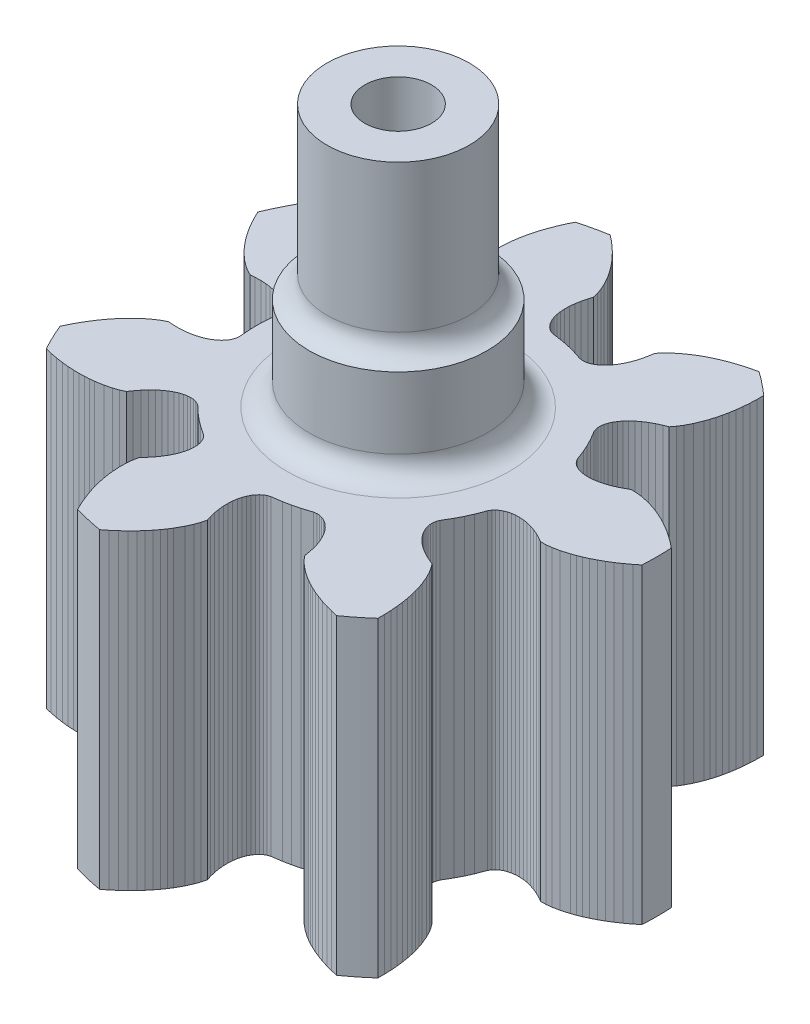
SolidWorks part; units mm, degrees
ref_plane "Front Plane" through (0, 0, 0) normal (0, 0, 1) x (1, 0, 0)
ref_plane "Top Plane" through (0, 0, 0) normal (0, 1, 0) x (1, 0, 0)
ref_plane "Right Plane" through (0, 0, 0) normal (1, 0, 0) x (0, 0, -1)
sketch "Sketch1" plane through (0, 0, 0) normal (0, 1, 0) x (1, 0, 0)
  circle A0 centre (0, 0) radius 2
  dimension "D1" = 4
extrude "Boss-Extrude1" add sketch "Sketch1" along normal blind 2.1
sketch "Sketch2" plane through (0, 2.1, 0) normal (0, 1, 0) x (1, 0, 0)
  circle A0 centre (0, 0) radius 1.6
  dimension "D1" = 3.2
extrude "Boss-Extrude3" add sketch "Sketch2" along normal blind 3.8
sketch "Sketch4" plane through (0, 0, 0) normal (0, -1, 0) x (1, 0, 0)
  line L420 (-1.6777, -5.4575) -> (-1.7402, -5.3144)
  line L421 (-1.7402, -5.3144) -> (-1.7939, -5.1757)
  line L422 (-1.7939, -5.1757) -> (-1.8392, -5.0423)
  line L423 (-1.8392, -5.0423) -> (-1.8764, -4.916)
  line L424 (-1.8764, -4.916) -> (-1.9071, -4.7932)
  line L425 (-1.9071, -4.7932) -> (-1.9311, -4.676)
  line L426 (-1.9311, -4.676) -> (-1.9488, -4.5668)
  line L427 (-1.9488, -4.5668) -> (-1.961, -4.464)
  line L428 (-1.961, -4.464) -> (-1.9715, -4.2798)
  line L429 (-1.9715, -4.2798) -> (-1.9674, -4.1246)
  line L430 (-1.9674, -4.1246) -> (-1.9537, -4.0009)
  line L431 (-1.9537, -4.0009) -> (-1.9303, -3.8867)
  line L432 (-1.9303, -3.8867) -> (-1.8594, -3.8097)
  line L433 (-1.8594, -3.8097) -> (-1.7784, -3.7125)
  line L434 (-1.7784, -3.7125) -> (-1.7087, -3.6155)
  line L435 (-1.7087, -3.6155) -> (-1.6501, -3.5195)
  line L436 (-1.6501, -3.5195) -> (-1.6023, -3.4251)
  line L437 (-1.6023, -3.4251) -> (-1.5652, -3.3333)
  line L438 (-1.5652, -3.3333) -> (-1.5384, -3.2446)
  line L439 (-1.5384, -3.2446) -> (-1.5215, -3.1597)
  line L440 (-1.5215, -3.1597) -> (-1.5143, -3.0795)
  line L441 (-1.5143, -3.0795) -> (-1.5162, -3.0043)
  line L442 (-1.5162, -3.0043) -> (-1.5269, -2.935)
  line L443 (-1.5269, -2.935) -> (-1.5457, -2.8721)
  line L444 (-1.5457, -2.8721) -> (-1.5723, -2.8162)
  line L445 (-1.5723, -2.8162) -> (-1.606, -2.7677)
  line L446 (-1.606, -2.7677) -> (-1.6572, -2.7183)
  line L447 (-1.6572, -2.7183) -> (-1.8447, -2.5928)
  line L448 (-1.8447, -2.5928) -> (-1.984, -2.4878)
  line L449 (-1.984, -2.4878) -> (-2.1173, -2.3754)
  line L450 (-2.1173, -2.3754) -> (-2.2814, -2.2205)
  line L451 (-2.2814, -2.2205) -> (-2.341, -2.1815)
  line L452 (-2.341, -2.1815) -> (-2.3957, -2.1595)
  line L453 (-2.3957, -2.1595) -> (-2.4562, -2.146)
  line L454 (-2.4562, -2.146) -> (-2.5217, -2.1417)
  line L455 (-2.5217, -2.1417) -> (-2.5917, -2.1467)
  line L456 (-2.5917, -2.1467) -> (-2.6653, -2.1615)
  line L457 (-2.6653, -2.1615) -> (-2.742, -2.1865)
  line L458 (-2.742, -2.1865) -> (-2.8209, -2.2218)
  line L459 (-2.8209, -2.2218) -> (-2.9014, -2.2676)
  line L460 (-2.9014, -2.2676) -> (-2.9827, -2.3243)
  line L461 (-2.9827, -2.3243) -> (-3.0641, -2.3918)
  line L462 (-3.0641, -2.3918) -> (-3.1447, -2.4703)
  line L463 (-3.1447, -2.4703) -> (-3.2237, -2.5599)
  line L464 (-3.2237, -2.5599) -> (-3.3005, -2.6605)
  line L465 (-3.3005, -2.6605) -> (-3.3598, -2.7467)
  line L466 (-3.3598, -2.7467) -> (-3.4659, -2.795)
  line L467 (-3.4659, -2.795) -> (-3.5835, -2.8358)
  line L468 (-3.5835, -2.8358) -> (-3.7338, -2.8744)
  line L469 (-3.7338, -2.8744) -> (-3.9158, -2.9052)
  line L470 (-3.9158, -2.9052) -> (-4.0187, -2.9161)
  line L471 (-4.0187, -2.9161) -> (-4.1291, -2.9232)
  line L472 (-4.1291, -2.9232) -> (-4.2487, -2.9258)
  line L473 (-4.2487, -2.9258) -> (-4.3752, -2.9233)
  line L474 (-4.3752, -2.9233) -> (-4.5067, -2.9151)
  line L475 (-4.5067, -2.9151) -> (-4.6468, -2.9006)
  line L476 (-4.6468, -2.9006) -> (-4.794, -2.8791)
  line L477 (-4.794, -2.8791) -> (-4.9474, -2.85)
  line L478 (-4.9474, -2.85) -> (-5.0902, -2.8167)
  line L479 (-5.3759, -2.2235) -> (-5.3129, -2.0911)
  line L480 (-5.3129, -2.0911) -> (-5.2399, -1.953)
  line L481 (-5.2399, -1.953) -> (-5.165, -1.8245)
  line L482 (-5.165, -1.8245) -> (-5.089, -1.7059)
  line L483 (-5.089, -1.7059) -> (-5.0134, -1.5981)
  line L484 (-5.0134, -1.5981) -> (-4.9365, -1.4976)
  line L485 (-4.9365, -1.4976) -> (-4.8599, -1.4057)
  line L486 (-4.8599, -1.4057) -> (-4.7855, -1.3238)
  line L487 (-4.7855, -1.3238) -> (-4.7128, -1.2502)
  line L488 (-4.7128, -1.2502) -> (-4.5753, -1.1271)
  line L489 (-4.5753, -1.1271) -> (-4.4514, -1.0336)
  line L490 (-4.4514, -1.0336) -> (-4.3462, -0.9671)
  line L491 (-4.3462, -0.9671) -> (-4.2422, -0.9142)
  line L492 (-4.2422, -0.9142) -> (-4.1379, -0.9217)
  line L493 (-4.1379, -0.9217) -> (-4.0114, -0.9244)
  line L494 (-4.0114, -0.9244) -> (-3.8921, -0.9184)
  line L495 (-3.8921, -0.9184) -> (-3.7804, -0.9043)
  line L496 (-3.7804, -0.9043) -> (-3.6769, -0.8828)
  line L497 (-3.6769, -0.8828) -> (-3.5819, -0.8546)
  line L498 (-3.5819, -0.8546) -> (-3.4959, -0.8203)
  line L499 (-3.4959, -0.8203) -> (-3.4191, -0.7805)
  line L500 (-3.4191, -0.7805) -> (-3.3518, -0.7361)
  line L501 (-3.3518, -0.7361) -> (-3.2942, -0.6878)
  line L502 (-3.2942, -0.6878) -> (-3.2467, -0.6363)
  line L503 (-3.2467, -0.6363) -> (-3.2093, -0.5823)
  line L504 (-3.2093, -0.5823) -> (-3.1821, -0.5267)
  line L505 (-3.1821, -0.5267) -> (-3.1652, -0.4701)
  line L506 (-3.1652, -0.4701) -> (-3.1585, -0.3992)
  line L507 (-3.1585, -0.3992) -> (-3.1773, -0.1744)
  line L508 (-3.1773, -0.1744) -> (-3.1821, 0)
  line L509 (-3.1821, 0) -> (-3.1773, 0.1743)
  line L510 (-3.1773, 0.1743) -> (-3.1585, 0.3991)
  line L511 (-3.1585, 0.3991) -> (-3.1652, 0.47)
  line L512 (-3.1652, 0.47) -> (-3.1821, 0.5266)
  line L513 (-3.1821, 0.5266) -> (-3.2093, 0.5822)
  line L514 (-3.2093, 0.5822) -> (-3.2467, 0.6362)
  line L515 (-3.2467, 0.6362) -> (-3.2942, 0.6877)
  line L516 (-3.2942, 0.6877) -> (-3.3518, 0.7361)
  line L517 (-3.3518, 0.7361) -> (-3.4191, 0.7805)
  line L518 (-3.4191, 0.7805) -> (-3.4959, 0.8202)
  line L519 (-3.4959, 0.8202) -> (-3.5819, 0.8545)
  line L520 (-3.5819, 0.8545) -> (-3.6769, 0.8828)
  line L521 (-3.6769, 0.8828) -> (-3.7804, 0.9043)
  line L522 (-3.7804, 0.9043) -> (-3.8921, 0.9183)
  line L523 (-3.8921, 0.9183) -> (-4.0114, 0.9243)
  line L524 (-4.0114, 0.9243) -> (-4.1379, 0.9216)
  line L525 (-4.1379, 0.9216) -> (-4.2422, 0.9142)
  line L526 (-4.2422, 0.9142) -> (-4.3462, 0.967)
  line L527 (-4.3462, 0.967) -> (-4.4514, 1.0335)
  line L528 (-4.4514, 1.0335) -> (-4.5753, 1.127)
  line L529 (-4.5753, 1.127) -> (-4.7128, 1.2501)
  line L530 (-4.7128, 1.2501) -> (-4.7855, 1.3238)
  line L531 (-4.7855, 1.3238) -> (-4.8599, 1.4056)
  line L532 (-4.8599, 1.4056) -> (-4.9365, 1.4975)
  line L533 (-4.9365, 1.4975) -> (-5.0134, 1.598)
  line L534 (-5.0134, 1.598) -> (-5.089, 1.7059)
  line L535 (-5.089, 1.7059) -> (-5.165, 1.8244)
  line L536 (-5.165, 1.8244) -> (-5.2399, 1.9529)
  line L537 (-5.2399, 1.9529) -> (-5.3129, 2.0911)
  line L538 (-5.3129, 2.0911) -> (-5.3759, 2.2234)
  line L539 (-5.0902, 2.8167) -> (-4.9474, 2.8499)
  line L540 (-4.9474, 2.8499) -> (-4.794, 2.879)
  line L541 (-4.794, 2.879) -> (-4.6468, 2.9005)
  line L542 (-4.6468, 2.9005) -> (-4.5067, 2.9151)
  line L543 (-4.5067, 2.9151) -> (-4.3752, 2.9232)
  line L544 (-4.3752, 2.9232) -> (-4.2487, 2.9257)
  line L545 (-4.2487, 2.9257) -> (-4.1291, 2.9231)
  line L546 (-4.1291, 2.9231) -> (-4.0187, 2.916)
  line L547 (-4.0187, 2.916) -> (-3.9158, 2.9051)
  line L548 (-3.9158, 2.9051) -> (-3.7338, 2.8743)
  line L549 (-3.7338, 2.8743) -> (-3.5835, 2.8358)
  line L550 (-3.5835, 2.8358) -> (-3.4659, 2.7949)
  line L551 (-3.4659, 2.7949) -> (-3.3598, 2.7466)
  line L552 (-3.3598, 2.7466) -> (-3.3005, 2.6604)
  line L553 (-3.3005, 2.6604) -> (-3.2237, 2.5598)
  line L554 (-3.2237, 2.5598) -> (-3.1447, 2.4703)
  line L555 (-3.1447, 2.4703) -> (-3.0641, 2.3918)
  line L556 (-3.0641, 2.3918) -> (-2.9827, 2.3242)
  line L557 (-2.9827, 2.3242) -> (-2.9014, 2.2676)
  line L558 (-2.9014, 2.2676) -> (-2.8209, 2.2217)
  line L559 (-2.8209, 2.2217) -> (-2.742, 2.1864)
  line L560 (-2.742, 2.1864) -> (-2.6653, 2.1615)
  line L561 (-2.6653, 2.1615) -> (-2.5917, 2.1466)
  line L562 (-2.5917, 2.1466) -> (-2.5217, 2.1416)
  line L563 (-2.5217, 2.1416) -> (-2.4562, 2.146)
  line L564 (-2.4562, 2.146) -> (-2.3957, 2.1594)
  line L565 (-2.3957, 2.1594) -> (-2.341, 2.1815)
  line L566 (-2.341, 2.1815) -> (-2.2814, 2.2205)
  line L567 (-2.2814, 2.2205) -> (-2.1173, 2.3753)
  line L568 (-2.1173, 2.3753) -> (-1.984, 2.4878)
  line L569 (-1.984, 2.4878) -> (-1.8447, 2.5927)
  line L570 (-1.8447, 2.5927) -> (-1.6572, 2.7182)
  line L571 (-1.6572, 2.7182) -> (-1.606, 2.7676)
  line L572 (-1.606, 2.7676) -> (-1.5723, 2.8161)
  line L573 (-1.5723, 2.8161) -> (-1.5457, 2.8721)
  line L574 (-1.5457, 2.8721) -> (-1.5269, 2.935)
  line L575 (-1.5269, 2.935) -> (-1.5162, 3.0043)
  line L576 (-1.5162, 3.0043) -> (-1.5143, 3.0794)
  line L577 (-1.5143, 3.0794) -> (-1.5215, 3.1597)
  line L578 (-1.5215, 3.1597) -> (-1.5384, 3.2445)
  line L579 (-1.5384, 3.2445) -> (-1.5652, 3.3332)
  line L580 (-1.5652, 3.3332) -> (-1.6023, 3.4251)
  line L581 (-1.6023, 3.4251) -> (-1.6501, 3.5194)
  line L582 (-1.6501, 3.5194) -> (-1.7087, 3.6154)
  line L583 (-1.7087, 3.6154) -> (-1.7784, 3.7125)
  line L584 (-1.7784, 3.7125) -> (-1.8594, 3.8097)
  line L585 (-1.8594, 3.8097) -> (-1.9303, 3.8866)
  line L586 (-1.9303, 3.8866) -> (-1.9537, 4.0009)
  line L587 (-1.9537, 4.0009) -> (-1.9674, 4.1246)
  line L588 (-1.9674, 4.1246) -> (-1.9715, 4.2797)
  line L589 (-1.9715, 4.2797) -> (-1.961, 4.464)
  line L590 (-1.961, 4.464) -> (-1.9488, 4.5668)
  line L591 (-1.9488, 4.5668) -> (-1.9311, 4.6759)
  line L592 (-1.9311, 4.6759) -> (-1.9071, 4.7932)
  line L593 (-1.9071, 4.7932) -> (-1.8764, 4.9159)
  line L594 (-1.8764, 4.9159) -> (-1.8392, 5.0423)
  line L595 (-1.8392, 5.0423) -> (-1.7939, 5.1756)
  line L596 (-1.7939, 5.1756) -> (-1.7402, 5.3143)
  line L597 (-1.7402, 5.3143) -> (-1.6777, 5.4575)
  line L598 (-1.6777, 5.4575) -> (-1.6135, 5.5893)
  line L599 (-0.9715, 5.7358) -> (-0.8565, 5.6449)
  line L600 (-0.8565, 5.6449) -> (-0.7381, 5.543)
  line L601 (-0.7381, 5.543) -> (-0.6295, 5.4414)
  line L602 (-0.6295, 5.4414) -> (-0.5308, 5.3409)
  line L603 (-0.5308, 5.3409) -> (-0.4425, 5.2432)
  line L604 (-0.4425, 5.2432) -> (-0.3616, 5.1459)
  line L605 (-0.3616, 5.1459) -> (-0.2891, 5.0507)
  line L606 (-0.2891, 5.0507) -> (-0.2258, 4.96)
  line L607 (-0.2258, 4.96) -> (-0.1702, 4.8727)
  line L608 (-0.1702, 4.8727) -> (-0.0808, 4.7113)
  line L609 (-0.0808, 4.7113) -> (-0.0172, 4.5697)
  line L610 (-0.0172, 4.5697) -> (0.0242, 4.4523)
  line L611 (0.0242, 4.4523) -> (0.0526, 4.3392)
  line L612 (0.0526, 4.3392) -> (0.0222, 4.2391)
  line L613 (0.0222, 4.2391) -> (-0.0086, 4.1164)
  line L614 (-0.0086, 4.1164) -> (-0.0293, 3.9987)
  line L615 (-0.0293, 3.9987) -> (-0.0405, 3.8868)
  line L616 (-0.0405, 3.8868) -> (-0.0426, 3.7811)
  line L617 (-0.0426, 3.7811) -> (-0.0362, 3.6822)
  line L618 (-0.0362, 3.6822) -> (-0.0218, 3.5907)
  line L619 (-0.0218, 3.5907) -> (-0.0002, 3.5069)
  line L620 (-0.0002, 3.5069) -> (0.0281, 3.4314)
  line L621 (0.0281, 3.4314) -> (0.0624, 3.3646)
  line L622 (0.0624, 3.3646) -> (0.1021, 3.3068)
  line L623 (0.1021, 3.3068) -> (0.1464, 3.2583)
  line L624 (0.1464, 3.2583) -> (0.1946, 3.2194)
  line L625 (0.1946, 3.2194) -> (0.246, 3.1903)
  line L626 (0.246, 3.1903) -> (0.3136, 3.1681)
  line L627 (0.3136, 3.1681) -> (0.537, 3.1363)
  line L628 (0.537, 3.1363) -> (0.708, 3.1022)
  line L629 (0.708, 3.1022) -> (0.8769, 3.0588)
  line L630 (0.8769, 3.0588) -> (1.0919, 2.9904)
  line L631 (1.0919, 2.9904) -> (1.1625, 2.9811)
  line L632 (1.1625, 2.9811) -> (1.2214, 2.985)
  line L633 (1.2214, 2.985) -> (1.2817, 2.9991)
  line L634 (1.2817, 2.9991) -> (1.3427, 3.0236)
  line L635 (1.3427, 3.0236) -> (1.4035, 3.0585)
  line L636 (1.4035, 3.0585) -> (1.4634, 3.1038)
  line L637 (1.4634, 3.1038) -> (1.5217, 3.1596)
  line L638 (1.5217, 3.1596) -> (1.5775, 3.2256)
  line L639 (1.5775, 3.2256) -> (1.6301, 3.3019)
  line L640 (1.6301, 3.3019) -> (1.6788, 3.3882)
  line L641 (1.6788, 3.3882) -> (1.7228, 3.4843)
  line L642 (1.7228, 3.4843) -> (1.7613, 3.59)
  line L643 (1.7613, 3.59) -> (1.7937, 3.705)
  line L644 (1.7937, 3.705) -> (1.8192, 3.829)
  line L645 (1.8192, 3.829) -> (1.8352, 3.9324)
  line L646 (1.8352, 3.9324) -> (1.9099, 4.0219)
  line L647 (1.9099, 4.0219) -> (1.9981, 4.1097)
  line L648 (1.9981, 4.1097) -> (2.1168, 4.2097)
  line L649 (2.1168, 4.2097) -> (2.2674, 4.3164)
  line L650 (2.2674, 4.3164) -> (2.3554, 4.3709)
  line L651 (2.3554, 4.3709) -> (2.4518, 4.4251)
  line L652 (2.4518, 4.4251) -> (2.5584, 4.4794)
  line L653 (2.5584, 4.4794) -> (2.6735, 4.532)
  line L654 (2.6735, 4.532) -> (2.7955, 4.5817)
  line L655 (2.7955, 4.5817) -> (2.928, 4.6294)
  line L656 (2.928, 4.6294) -> (3.0699, 4.6739)
  line L657 (3.0699, 4.6739) -> (3.2208, 4.7143)
  line L658 (3.2208, 4.7143) -> (3.3639, 4.7463)
  line L659 (3.8787, 4.3357) -> (3.8793, 4.1891)
  line L660 (3.8793, 4.1891) -> (3.8735, 4.033)
  line L661 (3.8735, 4.033) -> (3.8618, 3.8847)
  line L662 (3.8618, 3.8847) -> (3.8448, 3.7449)
  line L663 (3.8448, 3.7449) -> (3.8234, 3.615)
  line L664 (3.8234, 3.615) -> (3.7978, 3.4911)
  line L665 (3.7978, 3.4911) -> (3.7686, 3.375)
  line L666 (3.7686, 3.375) -> (3.7371, 3.269)
  line L667 (3.7371, 3.269) -> (3.7036, 3.1711)
  line L668 (3.7036, 3.1711) -> (3.6331, 3.0005)
  line L669 (3.6331, 3.0005) -> (3.562, 2.8625)
  line L670 (3.562, 2.8625) -> (3.4961, 2.757)
  line L671 (3.4961, 2.757) -> (3.4253, 2.6643)
  line L672 (3.4253, 2.6643) -> (3.3281, 2.6257)
  line L673 (3.3281, 2.6257) -> (3.213, 2.5732)
  line L674 (3.213, 2.5732) -> (3.1081, 2.516)
  line L675 (3.1081, 2.516) -> (3.0136, 2.4549)
  line L676 (3.0136, 2.4549) -> (2.9296, 2.3907)
  line L677 (2.9296, 2.3907) -> (2.8563, 2.324)
  line L678 (2.8563, 2.324) -> (2.7937, 2.2557)
  line L679 (2.7937, 2.2557) -> (2.7417, 2.1866)
  line L680 (2.7417, 2.1866) -> (2.7003, 2.1174)
  line L681 (2.7003, 2.1174) -> (2.6695, 2.0489)
  line L682 (2.6695, 2.0489) -> (2.649, 1.9819)
  line L683 (2.649, 1.9819) -> (2.6387, 1.917)
  line L684 (2.6387, 1.917) -> (2.6383, 1.8551)
  line L685 (2.6383, 1.8551) -> (2.6476, 1.7967)
  line L686 (2.6476, 1.7967) -> (2.6724, 1.73)
  line L687 (2.6724, 1.73) -> (2.7869, 1.5356)
  line L688 (2.7869, 1.5356) -> (2.8668, 1.3806)
  line L689 (2.8668, 1.3806) -> (2.9382, 1.2215)
  line L690 (2.9382, 1.2215) -> (3.0188, 1.0107)
  line L691 (3.0188, 1.0107) -> (3.0555, 0.9498)
  line L692 (3.0555, 0.9498) -> (3.0953, 0.9061)
  line L693 (3.0953, 0.9061) -> (3.144, 0.8678)
  line L694 (3.144, 0.8678) -> (3.2011, 0.8354)
  line L695 (3.2011, 0.8354) -> (3.2663, 0.8096)
  line L696 (3.2663, 0.8096) -> (3.3391, 0.791)
  line L697 (3.3391, 0.791) -> (3.419, 0.7802)
  line L698 (3.419, 0.7802) -> (3.5054, 0.7777)
  line L699 (3.5054, 0.7777) -> (3.5979, 0.7842)
  line L700 (3.5979, 0.7842) -> (3.6957, 0.7999)
  line L701 (3.6957, 0.7999) -> (3.7983, 0.8255)
  line L702 (3.7983, 0.8255) -> (3.905, 0.8612)
  line L703 (3.905, 0.8612) -> (4.0151, 0.9076)
  line L704 (4.0151, 0.9076) -> (4.1279, 0.9649)
  line L705 (4.1279, 0.9649) -> (4.2187, 1.0169)
  line L706 (4.2187, 1.0169) -> (4.3353, 1.0144)
  line L707 (4.3353, 1.0144) -> (4.4589, 1.0001)
  line L708 (4.4589, 1.0001) -> (4.6111, 0.9696)
  line L709 (4.6111, 0.9696) -> (4.7884, 0.9184)
  line L710 (4.7884, 0.9184) -> (4.8859, 0.8836)
  line L711 (4.8859, 0.8836) -> (4.9884, 0.8421)
  line L712 (4.9884, 0.8421) -> (5.0973, 0.7926)
  line L713 (5.0973, 0.7926) -> (5.2102, 0.7354)
  line L714 (5.2102, 0.7354) -> (5.3251, 0.671)
  line L715 (5.3251, 0.671) -> (5.445, 0.5972)
  line L716 (5.445, 0.5972) -> (5.5683, 0.5139)
  line L717 (5.5683, 0.5139) -> (5.6939, 0.4211)
  line L718 (5.6939, 0.4211) -> (5.8081, 0.3292)
  line L719 (5.8081, -0.3293) -> (5.6939, -0.4212)
  line L720 (5.6939, -0.4212) -> (5.5683, -0.514)
  line L721 (5.5683, -0.514) -> (5.445, -0.5972)
  line L722 (5.445, -0.5972) -> (5.3251, -0.6711)
  line L723 (5.3251, -0.6711) -> (5.2102, -0.7354)
  line L724 (5.2102, -0.7354) -> (5.0973, -0.7926)
  line L725 (5.0973, -0.7926) -> (4.9884, -0.8421)
  line L726 (4.9884, -0.8421) -> (4.8859, -0.8837)
  line L727 (4.8859, -0.8837) -> (4.7884, -0.9185)
  line L728 (4.7884, -0.9185) -> (4.6111, -0.9697)
  line L729 (4.6111, -0.9697) -> (4.4589, -1.0002)
  line L730 (4.4589, -1.0002) -> (4.3353, -1.0144)
  line L731 (4.3353, -1.0144) -> (4.2187, -1.017)
  line L732 (4.2187, -1.017) -> (4.1279, -0.965)
  line L733 (4.1279, -0.965) -> (4.0151, -0.9077)
  line L734 (4.0151, -0.9077) -> (3.905, -0.8613)
  line L735 (3.905, -0.8613) -> (3.7983, -0.8255)
  line L736 (3.7983, -0.8255) -> (3.6957, -0.8)
  line L737 (3.6957, -0.8) -> (3.5979, -0.7842)
  line L738 (3.5979, -0.7842) -> (3.5054, -0.7778)
  line L739 (3.5054, -0.7778) -> (3.419, -0.7803)
  line L740 (3.419, -0.7803) -> (3.3391, -0.7911)
  line L741 (3.3391, -0.7911) -> (3.2663, -0.8097)
  line L742 (3.2663, -0.8097) -> (3.2011, -0.8354)
  line L743 (3.2011, -0.8354) -> (3.144, -0.8678)
  line L744 (3.144, -0.8678) -> (3.0953, -0.9062)
  line L745 (3.0953, -0.9062) -> (3.0555, -0.9498)
  line L746 (3.0555, -0.9498) -> (3.0188, -1.0108)
  line L747 (3.0188, -1.0108) -> (2.9382, -1.2215)
  line L748 (2.9382, -1.2215) -> (2.8668, -1.3806)
  line L749 (2.8668, -1.3806) -> (2.7869, -1.5356)
  line L750 (2.7869, -1.5356) -> (2.6724, -1.7301)
  line L751 (2.6724, -1.7301) -> (2.6476, -1.7968)
  line L752 (2.6476, -1.7968) -> (2.6383, -1.8551)
  line L753 (2.6383, -1.8551) -> (2.6387, -1.9171)
  line L754 (2.6387, -1.9171) -> (2.649, -1.9819)
  line L755 (2.649, -1.9819) -> (2.6695, -2.049)
  line L756 (2.6695, -2.049) -> (2.7003, -2.1175)
  line L757 (2.7003, -2.1175) -> (2.7417, -2.1867)
  line L758 (2.7417, -2.1867) -> (2.7937, -2.2558)
  line L759 (2.7937, -2.2558) -> (2.8563, -2.3241)
  line L760 (2.8563, -2.3241) -> (2.9296, -2.3907)
  line L761 (2.9296, -2.3907) -> (3.0136, -2.455)
  line L762 (3.0136, -2.455) -> (3.1081, -2.5161)
  line L763 (3.1081, -2.5161) -> (3.213, -2.5733)
  line L764 (3.213, -2.5733) -> (3.3281, -2.6257)
  line L765 (3.3281, -2.6257) -> (3.4253, -2.6643)
  line L766 (3.4253, -2.6643) -> (3.4961, -2.757)
  line L767 (3.4961, -2.757) -> (3.562, -2.8626)
  line L768 (3.562, -2.8626) -> (3.6331, -3.0006)
  line L769 (3.6331, -3.0006) -> (3.7036, -3.1711)
  line L770 (3.7036, -3.1711) -> (3.7371, -3.2691)
  line L771 (3.7371, -3.2691) -> (3.7686, -3.3751)
  line L772 (3.7686, -3.3751) -> (3.7978, -3.4911)
  line L773 (3.7978, -3.4911) -> (3.8234, -3.615)
  line L774 (3.8234, -3.615) -> (3.8448, -3.745)
  line L775 (3.8448, -3.745) -> (3.8618, -3.8848)
  line L776 (3.8618, -3.8848) -> (3.8735, -4.0331)
  line L777 (3.8735, -4.0331) -> (3.8793, -4.1892)
  line L778 (3.8793, -4.1892) -> (3.8787, -4.3358)
  line L779 (3.3639, -4.7463) -> (3.2208, -4.7143)
  line L780 (3.2208, -4.7143) -> (3.0699, -4.6739)
  line L781 (3.0699, -4.6739) -> (2.928, -4.6295)
  line L782 (2.928, -4.6295) -> (2.7955, -4.5818)
  line L783 (2.7955, -4.5818) -> (2.6735, -4.5321)
  line L784 (2.6735, -4.5321) -> (2.5584, -4.4795)
  line L785 (2.5584, -4.4795) -> (2.4518, -4.4252)
  line L786 (2.4518, -4.4252) -> (2.3554, -4.3709)
  line L787 (2.3554, -4.3709) -> (2.2674, -4.3164)
  line L788 (2.2674, -4.3164) -> (2.1168, -4.2097)
  line L789 (2.1168, -4.2097) -> (1.9981, -4.1098)
  line L790 (1.9981, -4.1098) -> (1.9099, -4.022)
  line L791 (1.9099, -4.022) -> (1.8352, -3.9324)
  line L792 (1.8352, -3.9324) -> (1.8192, -3.829)
  line L793 (1.8192, -3.829) -> (1.7937, -3.7051)
  line L794 (1.7937, -3.7051) -> (1.7613, -3.5901)
  line L795 (1.7613, -3.5901) -> (1.7228, -3.4844)
  line L796 (1.7228, -3.4844) -> (1.6788, -3.3883)
  line L797 (1.6788, -3.3883) -> (1.6301, -3.3019)
  line L798 (1.6301, -3.3019) -> (1.5775, -3.2257)
  line L799 (1.5775, -3.2257) -> (1.5217, -3.1596)
  line L800 (1.5217, -3.1596) -> (1.4634, -3.1039)
  line L801 (1.4634, -3.1039) -> (1.4035, -3.0586)
  line L802 (1.4035, -3.0586) -> (1.3427, -3.0237)
  line L803 (1.3427, -3.0237) -> (1.2817, -2.9992)
  line L804 (1.2817, -2.9992) -> (1.2214, -2.9851)
  line L805 (1.2214, -2.9851) -> (1.1625, -2.9812)
  line L806 (1.1625, -2.9812) -> (1.0919, -2.9905)
  line L807 (1.0919, -2.9905) -> (0.8769, -3.0588)
  line L808 (0.8769, -3.0588) -> (0.708, -3.1023)
  line L809 (0.708, -3.1023) -> (0.537, -3.1364)
  line L810 (0.537, -3.1364) -> (0.3136, -3.1681)
  line L811 (0.3136, -3.1681) -> (0.246, -3.1904)
  line L812 (0.246, -3.1904) -> (0.1946, -3.2194)
  line L813 (0.1946, -3.2194) -> (0.1464, -3.2583)
  line L814 (0.1464, -3.2583) -> (0.1021, -3.3068)
  line L815 (0.1021, -3.3068) -> (0.0624, -3.3647)
  line L816 (0.0624, -3.3647) -> (0.0281, -3.4315)
  line L817 (0.0281, -3.4315) -> (-0.0002, -3.507)
  line L818 (-0.0002, -3.507) -> (-0.0218, -3.5907)
  line L819 (-0.0218, -3.5907) -> (-0.0362, -3.6823)
  line L820 (-0.0362, -3.6823) -> (-0.0426, -3.7811)
  line L821 (-0.0426, -3.7811) -> (-0.0405, -3.8868)
  line L822 (-0.0405, -3.8868) -> (-0.0293, -3.9988)
  line L823 (-0.0293, -3.9988) -> (-0.0086, -4.1165)
  line L824 (-0.0086, -4.1165) -> (0.0222, -4.2392)
  line L825 (0.0222, -4.2392) -> (0.0526, -4.3393)
  line L826 (0.0526, -4.3393) -> (0.0242, -4.4524)
  line L827 (0.0242, -4.4524) -> (-0.0172, -4.5698)
  line L828 (-0.0172, -4.5698) -> (-0.0808, -4.7113)
  line L829 (-0.0808, -4.7113) -> (-0.1702, -4.8728)
  line L830 (-0.1702, -4.8728) -> (-0.2258, -4.9601)
  line L831 (-0.2258, -4.9601) -> (-0.2891, -5.0508)
  line L832 (-0.2891, -5.0508) -> (-0.3616, -5.146)
  line L833 (-0.3616, -5.146) -> (-0.4425, -5.2433)
  line L834 (-0.4425, -5.2433) -> (-0.5308, -5.341)
  line L835 (-0.5308, -5.341) -> (-0.6295, -5.4414)
  line L836 (-0.6295, -5.4414) -> (-0.7381, -5.5431)
  line L837 (-0.7381, -5.5431) -> (-0.8565, -5.645)
  line L838 (-0.8565, -5.645) -> (-0.9715, -5.7359)
  line L839 (-1.6135, -5.5894) -> (-1.6777, -5.4575)
  arc A7 (-5.3759, -2.2235) -> (-5.0902, -2.8167) centre (0, 0) ccw
  arc A8 (-5.0902, 2.8167) -> (-5.3759, 2.2234) centre (0, -0.0001) ccw
  arc A9 (-0.9715, 5.7358) -> (-1.6135, 5.5893) centre (0, -0.0001) ccw
  arc A10 (3.8787, 4.3357) -> (3.3639, 4.7463) centre (-0.0001, -0.0001) ccw
  arc A11 (5.8081, -0.3293) -> (5.8081, 0.3292) centre (-0.0001, 0) ccw
  arc A12 (3.3639, -4.7463) -> (3.8787, -4.3358) centre (-0.0001, 0) ccw
  arc A13 (-1.6135, -5.5894) -> (-0.9715, -5.7359) centre (0, 0) ccw
extrude "Boss-Extrude4" add sketch "Sketch4" along normal blind 7
sketch "Sketch3" plane through (0, 0, 0) normal (0, -1, 0) x (1, 0, 0)
  circle A0 centre (0, 0) radius 1.1
  circle A1 centre (0, 0) radius 0.75
  dimension "D1" = 2.2
  dimension "D2" = 1.5
extrude "Cut-Extrude1" cut sketch "Sketch3" against normal through all contours A1
extrude "Cut-Extrude2" cut sketch "Sketch3<3>" along normal through all contours A0 A1 | A1 region at (-1.0689, 0, 0) region at (0, 0, 0)
sketch "Sketch3<3>" plane through (0, 0, 0) normal (0, -1, 0) x (1, 0, 0) same geometry as "Sketch3"
fillet "Fillet1" radius 0.5 2 edges at (0, 2.1, 1.6) (0, 0, -2)
chamfer "Chamfer1" distance 0.4 angle 45 2 edges at (0, 0, 1.1) (0, -7, 1.1)
